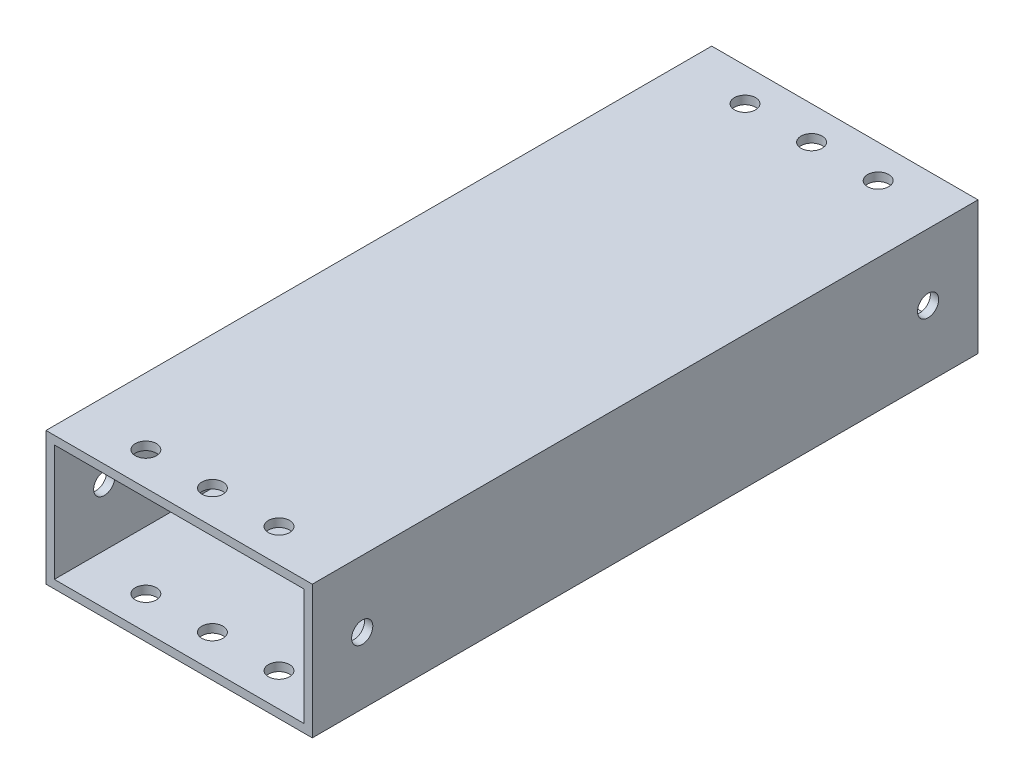
SolidWorks part; units mm, degrees
ref_plane "Front Plane" through (0, 0, 0) normal (0, 0, 1) x (1, 0, 0)
ref_plane "Top Plane" through (0, 0, 0) normal (0, 1, 0) x (1, 0, 0)
ref_plane "Right Plane" through (0, 0, 0) normal (1, 0, 0) x (0, 0, -1)
sketch "Sketch1" plane through (0, 0, 0) normal (0, 0, 1) x (1, 0, 0)
  line L0 (-23.8125, 11.1125) -> (23.8125, 11.1125)
  line L1 (-25.4, -12.7) -> (25.4, -12.7)
  line L2 (-25.4, -12.7) -> (-25.4, 12.7)
  line L3 (-25.4, 12.7) -> (25.4, 12.7)
  line L4 (25.4, -12.7) -> (25.4, 12.7)
  line L5 (-25.4, -12.7) -> (25.4, 12.7) construction
  line L6 (-25.4, 12.7) -> (25.4, -12.7) construction
  line L7 (23.8125, -11.1125) -> (23.8125, 11.1125)
  line L8 (-23.8125, -11.1125) -> (23.8125, -11.1125)
  line L9 (-23.8125, -11.1125) -> (-23.8125, 11.1125)
  point P0 (0, 0)
  dimension "D1" = 50.8
  dimension "D2" = 25.4
  dimension "D3" = 1.5875
extrude "Boss-Extrude1" add sketch "Sketch1" along normal mid plane 127
sketch "Sketch2" plane through (0, 12.7, 0) normal (0, 1, 0) x (1, 0, 0)
  line L0 (25.4, 63.5) -> (-25.4, 63.5) construction
  line L1 (25.4, 0) -> (-25.4, 0) construction
  line L2 (25.4, -63.5) -> (25.4, 63.5) construction
  line L3 (-25.4, -63.5) -> (-25.4, 63.5) construction
  circle A0 centre (-12.7, 57.15) radius 2.0193
  circle A1 centre (0, 57.15) radius 2.0193
  circle A2 centre (12.7, 57.15) radius 2.0193
  circle A3 centre (12.7, -57.15) radius 2.0193
  circle A4 centre (0, -57.15) radius 2.0193
  circle A5 centre (-12.7, -57.15) radius 2.0193
  dimension "D1" = 4.0386
  dimension "D2" = 12.7
  dimension "D3" = 12.7
  dimension "D4" = 6.35
extrude "Cut-Extrude1" cut sketch "Sketch2" against normal through all
sketch "Sketch3" plane through (25.4, 0, 0) normal (1, 0, 0) x (0, 0, -1)
  line L0 (0, 12.7) -> (0, -12.7) construction
  line L1 (-63.5, 12.7) -> (63.5, 12.7) construction
  line L2 (-63.5, -12.7) -> (63.5, -12.7) construction
  line L3 (-63.5, -12.7) -> (-63.5, 12.7) construction
  circle A0 centre (-53.975, 0) radius 2.0193
  circle A1 centre (53.975, 0) radius 2.0193
  point P12 (0, 0)
  dimension "D1" = 4.0386
  dimension "D2" = 9.525
extrude "Cut-Extrude2" cut sketch "Sketch3" against normal through all
